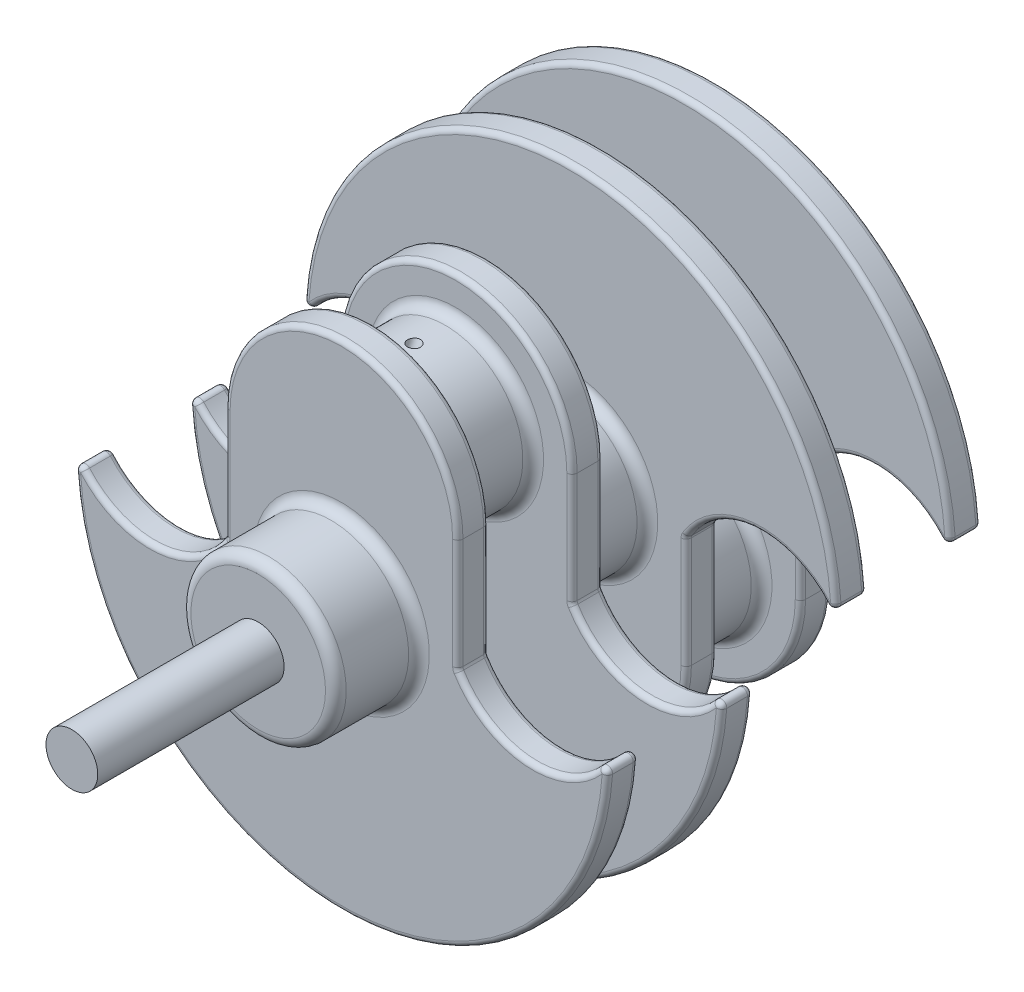
SolidWorks part; units mm, degrees
material "AISI 4340 Steel, normalized"
ref_plane "Front Plane" through (0, 0, 0) normal (0, 0, 1) x (1, 0, 0)
ref_plane "Top Plane" through (0, 0, 0) normal (0, 1, 0) x (1, 0, 0)
ref_plane "Right Plane" through (0, 0, 0) normal (1, 0, 0) x (0, 0, -1)
sketch "Sketch1" plane through (0, 0, 0) normal (0, 0, 1) x (1, 0, 0)
  circle A0 centre (0, 0) radius 30
  dimension "D1" = 30
extrude "Boss-Extrude1" add sketch "Sketch1" along normal blind 32.13
sketch "Sketch8" plane through (0, 0, 0) normal (0, 0, -1) x (-1, 0, 0)
  line L0 (-45, 43.2) -> (-45, 0)
  line L1 (45, 43.2) -> (45, 0)
  line L2 (-45, 0) -> (-89.1072, 0) construction
  arc A0 (45, 43.2) -> (-45, 43.2) centre (0, 43.2) ccw
  arc A5 (-103, 0) -> (103, 0) centre (0, 0) ccw
  arc A6 (-45, 0) -> (-103, 0) centre (-74, 16.8638) cw
  arc A7 (45, 0) -> (103, 0) centre (74, 16.8638) ccw
  dimension "D1" = 45
  dimension "D2" = 103
  dimension "D3" = 43.2
  dimension "D4" = 0
  dimension "D5" = 180
  dimension "D6" = 0
extrude "Boss-Extrude5" add sketch "Sketch8" along normal blind 12
sketch "Sketch2" plane through (0, 0, 32.13) normal (0, 0, 1) x (1, 0, 0)
  circle A0 centre (0, 0) radius 10
  dimension "D1" = 10
extrude "Boss-Extrude2" add sketch "Sketch2" along normal blind 20
sketch "Sketch9" plane through (0, 0, -12) normal (0, 0, -1) x (-1, 0, 0)
  circle A0 centre (0, 43.2) radius 30
  dimension "D2" = 30
  dimension "D1" = 43.2
extrude "Boss-Extrude6" add sketch "Sketch9" along normal blind 32.13
ref_plane "Plane4" through (0, 0, -88.26) normal (0, 0, -1) x (-1, 0, 0)
sketch "Sketch10" plane through (0, 0, -44.13) normal (0, 0, -1) x (-1, 0, 0)
  line L0 (-45, -43.2) -> (-45, 0)
  line L1 (45, -43.2) -> (45, 0)
  line L2 (45, 0) -> (85.967, 0) construction
  arc A0 (-45, -43.2) -> (45, -43.2) centre (0, -43.2) ccw
  arc A1 (-45, 0) -> (-103, 0) centre (-74, -16.8638) ccw
  arc A2 (45, 0) -> (103, 0) centre (74, -16.8638) cw
  arc A3 (-103, 0) -> (103, 0) centre (0, 0) cw
  dimension "D1" = 45
  dimension "D4" = 0
  dimension "D5" = 180
  dimension "D6" = 0
  dimension "D3" = 103
  dimension "D2" = 43.2
extrude "Boss-Extrude7" add sketch "Sketch10" along normal blind 12 from surface starting at plane "Plane4"
ref_plane "Plane3" through (0, 0, -132.39) normal (0, 0, -1) x (-1, 0, 0)
sketch "Sketch12" plane through (0, 0, -132.39) normal (0, 0, -1) x (-1, 0, 0)
  line L2 (45, -43.2) -> (45, 0)
  line L3 (45, -43.2) -> (45, 0)
  line L4 (-45, 0) -> (-45, -43.2)
  line L5 (-45, 0) -> (-45, -43.2)
  arc A12 (-45, -43.2) -> (45, -43.2) centre (0, -43.2) ccw
  arc A13 (103, 0) -> (45, 0) centre (74, -16.8638) ccw
  arc A14 (103, 0) -> (-103, 0) centre (0, 0) ccw
  arc A15 (-45, 0) -> (-103, 0) centre (-74, -16.8638) ccw
  arc A16 (-45, -43.2) -> (45, -43.2) centre (0, -43.2) ccw
  arc A17 (103, 0) -> (45, 0) centre (74, -16.8638) ccw
  arc A18 (103, 0) -> (-103, 0) centre (0, 0) ccw
  arc A19 (-45, 0) -> (-103, 0) centre (-74, -16.8638) ccw
  dimension "D1" = 0
extrude "Boss-Extrude8" add sketch "Sketch12" along normal blind 12
sketch "Sketch14" plane through (0, 0, -100.26) normal (0, 0, -1) x (-1, 0, 0)
  circle A0 centre (0, -43.2) radius 30
  dimension "D2" = 30
  dimension "D1" = 43.2
extrude "Boss-Extrude9" add sketch "Sketch14" along normal up to next
sketch "Sketch15" plane through (0, 0, -144.39) normal (0, 0, -1) x (-1, 0, 0)
  circle A1 centre (0, 0) radius 30
  circle A2 centre (0, 0) radius 30
  dimension "D1" = 0
extrude "Boss-Extrude10" add sketch "Sketch15" along normal blind 32.13
sketch "Sketch16" plane through (0, 0, -176.52) normal (0, 0, -1) x (-1, 0, 0)
  circle A1 centre (0, 0) radius 10
  circle A2 centre (0, 0) radius 10
  dimension "D1" = 0
extrude "Boss-Extrude11" add sketch "Sketch16" along normal blind 20
sketch "Sketch18" plane through (0, 0, -44.13) normal (0, 0, -1) x (-1, 0, 0)
  line L2 (-45, 43.2) -> (-45, 0)
  line L3 (-45, 43.2) -> (-45, 0)
  line L4 (45, 0) -> (45, 43.2)
  line L5 (45, 0) -> (45, 43.2)
  arc A4 (45, 43.2) -> (-45, 43.2) centre (0, 43.2) ccw
  arc A5 (-103, 0) -> (-45, 0) centre (-74, 16.8638) ccw
  arc A6 (-103, 0) -> (103, 0) centre (0, 0) ccw
  arc A7 (45, 0) -> (103, 0) centre (74, 16.8638) ccw
  arc A8 (45, 43.2) -> (-45, 43.2) centre (0, 43.2) ccw
  arc A9 (-103, 0) -> (-45, 0) centre (-74, 16.8638) ccw
  arc A10 (-103, 0) -> (103, 0) centre (0, 0) ccw
  arc A11 (45, 0) -> (103, 0) centre (74, 16.8638) ccw
  dimension "D1" = 0
extrude "Boss-Extrude12" add sketch "Sketch18" along normal blind 12
sketch "Sketch19" plane through (0, 0, -56.13) normal (0, 0, -1) x (-1, 0, 0)
  circle A1 centre (0, 0) radius 30
  circle A2 centre (0, 0) radius 30
  dimension "D1" = 0
extrude "Boss-Extrude13" add sketch "Sketch19" along normal up to next
fillet "Fillet1" radius 2 32 edges at (0, -103, -44.13) (-74, -16.683, -44.13) (-45, 21.6, -44.13) (45, 21.6, -44.13) (74, -16.683, -44.13) (0, -103, -56.13) (-74, -16.683, -56.13) (-45, 21.6, -56.13) (0, 88.2, -56.13) (45, 21.6, -56.13) (74, -16.683, -56.13) (103, 0, -50.13) (45, 0, -50.13) (-45, 0, -50.13) (-103, 0, -50.13) (0, 88.2, -44.13) (45, 21.6, 0) (74, -16.683, 0) (0, -103, 0) (-74, -16.683, 0) (-45, 21.6, 0) (0, 88.2, -12) (45, 21.6, -12) (74, -16.683, -12) (0, -103, -12) (-74, -16.683, -12) (-45, 21.6, -12) (-45, 0, -6) (-103, 0, -6) (103, 0, -6) (45, 0, -6) (0, 88.2, 0)
fillet "Fillet2" radius 2 16 edges at (0, 103, -132.39) (74, 16.683, -132.39) (45, -21.6, -132.39) (0, -88.2, -132.39) (-45, -21.6, -132.39) (-74, 16.683, -132.39) (74, 16.683, -144.39) (45, -21.6, -144.39) (0, -88.2, -144.39) (-45, -21.6, -144.39) (-74, 16.683, -144.39) (-103, 0, -138.39) (-45, 0, -138.39) (45, 0, -138.39) (103, 0, -138.39) (0, 103, -144.39)
fillet "Fillet3" radius 2 16 edges at (45, -21.6, -88.26) (74, 16.683, -88.26) (0, 103, -88.26) (-74, 16.683, -88.26) (-45, -21.6, -88.26) (0, -88.2, -88.26) (45, -21.6, -100.26) (74, 16.683, -100.26) (-74, 16.683, -100.26) (-45, -21.6, -100.26) (0, -88.2, -100.26) (45, 0, -94.26) (103, 0, -94.26) (-103, 0, -94.26) (-45, 0, -94.26) (0, 103, -100.26)
fillet "Fillet5" radius 4 2 edges at (30, 0, 32.13) (30, 0, 0)
fillet "Fillet6" radius 4 2 edges at (-30, 0, -144.39) (-30, 0, -176.52)
ref_plane "Plane5" through (0, 31.75, 0) normal (0, 1, 0) x (1, 0, 0)
sketch "Sketch20" plane through (0, 0, 0) normal (1, 0, 0) x (0, 0, -1)
  line L1 (100.26, -73.2) -> (100.26, -13.2)
  line L2 (100.26, -73.2) -> (100.26, -13.2)
  dimension "D1" = 0
ref_plane "Plane6" through (0, -73.2, 0) normal (0, 1, 0) x (1, 0, 0)
sketch "Sketch21" plane through (0, 31.75, 0) normal (0, 1, 0) x (1, 0, 0)
  line L2 (-30, 172.52) -> (30, 172.52) construction
  line L3 (-30, 172.52) -> (-30, 148.39) construction
  line L4 (-30, 148.39) -> (30, 148.39) construction
  line L5 (30, 172.52) -> (30, 148.39) construction
  circle A0 centre (0, 160.455) radius 2.5
  point P10 (0, 172.52)
  point P11 (30, 160.455)
  dimension "D1" = 5
sketch "Sketch27" plane through (0, 0, 0) normal (0, 0, 1) x (1, 0, 0)
  line L0 (0, 73.2) -> (0, -30) construction
  circle A1 centre (0, 43.2) radius 30
  circle A2 centre (0, 43.2) radius 30 construction
  circle A3 centre (0, 0) radius 30
  circle A4 centre (0, 0) radius 30 construction
  dimension "D1" = 0
  dimension "D2" = 0
ref_plane "Plane8" through (0, 73.2, 0) normal (0, -1, 0) x (-1, 0, 0)
ref_plane "Plane9" through (0, -30, 0) normal (0, -1, 0) x (-1, 0, 0)
sketch "Sketch28" plane through (0, -30, 0) normal (0, -1, 0) x (-1, 0, 0)
  line L1 (-30, -4) -> (30, -4) construction
  line L2 (-30, -4) -> (-30, -28.13) construction
  line L3 (-30, -28.13) -> (30, -28.13) construction
  line L4 (30, -4) -> (30, -28.13) construction
  line L5 (-30, -4) -> (30, -28.13) construction
  line L6 (-30, -28.13) -> (30, -4) construction
  circle A0 centre (0, -16.065) radius 2.5
  point P4 (0, -16.065)
  dimension "D1" = 5
sketch "Sketch29" plane through (0, 73.2, 0) normal (0, -1, 0) x (-1, 0, 0)
  line L1 (30, 44.13) -> (-30, 44.13) construction
  line L2 (30, 44.13) -> (30, 12) construction
  line L3 (30, 12) -> (-30, 12) construction
  line L4 (-30, 44.13) -> (-30, 12) construction
  line L5 (30, 44.13) -> (-30, 12) construction
  line L6 (30, 12) -> (-30, 44.13) construction
  circle A0 centre (0, 28.065) radius 2.5
  point P4 (0, 28.065)
sketch "Sketch31" plane through (0, 0, 0) normal (1, 0, 0) x (0, 0, -1)
  line L0 (28.065, 73.2) -> (-16.065, -30) construction
  line L1 (44.13, 86.2) -> (44.13, 43.2) construction
  line L2 (12, 43.2) -> (12, 86.2) construction
  line L3 (44.13, 86.2) -> (44.13, 43.2) construction
  line L4 (12, 43.2) -> (12, 86.2) construction
  dimension "D1" = 16.065
ref_plane "Plane10" through (0, 73.2, -28.065) normal (0, -0.9195, 0.3932) x (-1, 0, 0)
ref_plane "Plane11" through (0, -30, 16.065) normal (0, -0.9195, 0.3932) x (-1, 0, 0)
combine bodies "Combine1" operation type add bodies to combine 119 109 117
fillet "Fillet7" radius 4 6 edges at (-30, 43.2, -44.13) (-30, 43.2, -12) (-30, 0, -56.13) (-30, 0, -88.26) (-30, -43.2, -132.39) (-30, -43.2, -100.26)
sketch "Sketch39" plane through (0, -73.2, 0) normal (0, 1, 0) x (1, 0, 0)
  line L1 (30, 128.39) -> (-30, 128.39) construction
  line L2 (30, 128.39) -> (30, 104.26) construction
  line L3 (30, 104.26) -> (-30, 104.26) construction
  line L4 (-30, 128.39) -> (-30, 104.26) construction
  line L5 (30, 128.39) -> (-30, 104.26) construction
  line L6 (30, 104.26) -> (-30, 128.39) construction
  point P4 (0, 116.325)
sketch "Sketch40" plane through (0, 0, 0) normal (1, 0, 0) x (0, 0, -1)
  line L0 (160.455, 31.75) -> (116.325, -73.2) construction
  line L1 (172.52, 31.75) -> (148.39, 31.75) construction
  line L3 (132.39, -43.2) -> (132.39, -86.2) construction
  dimension "D1" = 16.065
ref_plane "Plane12" through (0, 31.75, -160.455) normal (0, -0.9218, 0.3876) x (-1, 0, 0)
ref_plane "Plane13" through (0, -73.2, -116.325) normal (0, -0.9218, 0.3876) x (-1, 0, 0)
sketch "Sketch47" plane through (0, 73.2, -28.065) normal (0, -0.9195, 0.3932) x (-1, 0, 0)
  ellipse E0 centre (0, 0) end of major axis (2.5, 0) minor radius 2.2987 construction
  ellipse E1 centre (0, 0) end of major axis (2.5, 0) minor radius 2.2987
sketch "Sketch48" plane through (0, -30, 16.065) normal (0, -0.9195, 0.3932) x (-1, 0, 0)
  ellipse E0 centre (0, 0) end of major axis (2.5, 0) minor radius 2.2987 construction
  ellipse E1 centre (0, 0) end of major axis (2.5, 0) minor radius 2.2987
extrude "Cut-Extrude2" cut sketch "Sketch48" against normal through all
sketch "Sketch49" plane through (0, -73.2, -116.325) normal (0, -0.9218, 0.3876) x (-1, 0, 0)
  circle A0 centre (0, 0) radius 2.5
  dimension "D1" = 5
extrude "Cut-Extrude3" cut sketch "Sketch49" against normal through all
sketch "Sketch50" plane through (0, 31.75, -160.455) normal (0, -0.9218, 0.3876) x (-1, 0, 0)
  circle A0 centre (0, 0) radius 2.5 construction
  circle A1 centre (0, 0) radius 2.5
extrude "Cut-Extrude4" cut sketch "Sketch50" along normal through all
sketch "Sketch51" plane through (0, 0, 0) normal (1, 0, 0) x (0, 0, -1)
  line L0 (28.065, 73.2) -> (116.325, -73.2) construction
ref_plane "Plane14" through (0, 73.2, -28.065) normal (0, -0.8564, -0.5163) x (-1, 0, 0)
sketch "Sketch52" plane through (0, 73.2, -28.065) normal (0, -0.9195, 0.3932) x (-1, 0, 0)
  ellipse E0 centre (0, 0) end of major axis (2.5, 0) minor radius 2.2987 construction
  ellipse E1 centre (0, 0) end of major axis (2.5, 0) minor radius 2.2987
extrude "Cut-Extrude5" cut sketch "Sketch52" along normal through all and the other way through all
sketch "Sketch53" plane through (0, 0, 52.13) normal (0, 0, -1) x (-1, 0, 0)
  circle A1 centre (0, 0) radius 10
  circle A2 centre (0, 0) radius 10
  dimension "D1" = 0
extrude "Boss-Extrude14" add sketch "Sketch53" against normal blind 52
equation "\"CRR\"= 43.2mm'Crank Radius"
equation "\"D1@Sketch9\"=\"CRR\""
equation "\"D1@Sketch14\"=\"CRR\""
equation "\"JR\"= 30mm'Journal Radius"
equation "\"D1@Sketch1\"=\"JR\""
equation "\"D2@Sketch9\"=\"JR\""
equation "\"D2@Sketch14\"=\"JR\""
equation "\"LT\"= 12mm'Lobe Thickness"
equation "\"D1@Boss-Extrude5\"=\"LT\""
equation "\"D1@Boss-Extrude7\"=\"LT\""
equation "\"D1@Boss-Extrude8\"=\"LT\""
equation "\"D1@Boss-Extrude12\"=\"LT\""
equation "\"D3@Sketch8\"=\"CRR\""
equation "\"D2@Sketch10\"=\"CRR\""
equation "\"JL\"= 24.13 + 2 * ( \"JF\" )'Journal Length"
equation "\"D1@Boss-Extrude1\"=\"JL\""
equation "\"D1@Boss-Extrude6\"=\"JL\""
equation "\"D1@Boss-Extrude10\"=\"JL\""
equation "\"LHD\"= 5mm'Lubrication Hole Diameter"
equation "\"D1@Sketch29\"=\"LHD\""
equation "\"JF\"= 4mm'Internal Journal Fillets"
equation "\"D1@Fillet7\"=\"JF\""
equation "\"D1@Fillet6\"=\"JF\""
equation "\"LR\"= 45mm'Lobe radius"
equation "\"CWR\"= 103mm'Counterweight Radius"
equation "\"D1@Sketch8\"=\"LR\""
equation "\"D2@Sketch8\"=\"CWR\""
equation "\"D3@Sketch10\"=\"CWR\""
equation "\"D1@Sketch10\"=\"LR\""
equation "\"CWA\"= 3.14159rad'Counterweight Arc"
equation "\"CWS\"= 0rad'Counterweight Slope"
equation "\"CWH\"= 0mm'Counterweight Offset"
equation "\"D4@Sketch8\"=\"CWH\""
equation "\"D5@Sketch8\"=\"CWA\""
equation "\"D6@Sketch8\"=\"CWS\""
equation "\"D4@Sketch10\"=\"CWH\""
equation "\"D5@Sketch10\"=\"CWA\""
equation "\"D6@Sketch10\"=\"CWS\""
